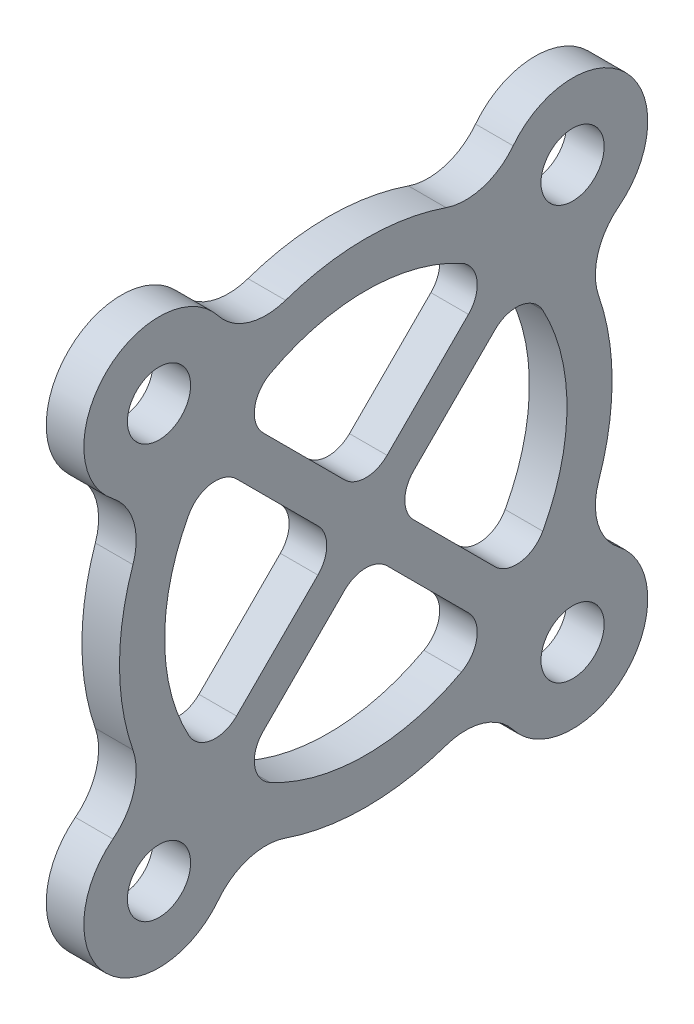
SolidWorks part; units mm, degrees
material "AR500"
ref_plane "Front Plane" through (0, 0, 0) normal (0, 0, 1) x (1, 0, 0)
ref_plane "Top Plane" through (0, 0, 0) normal (0, 1, 0) x (1, 0, 0)
ref_plane "Right Plane" through (0, 0, 0) normal (1, 0, 0) x (0, 0, -1)
ref_plane "Plane1" through (-36.325, 0, 0) normal (-1, 0, 0) x (0, 0, 1)
sketch "Sketch1" plane through (-36.325, 0, 0) normal (-1, 0, 0) x (0, 0, 1)
  arc A0 (-11.1136, 17.582) -> (-17.582, 11.1136) centre (-17.4625, 17.4625) ccw
  arc A1 (-17.582, -11.1136) -> (-11.1136, -17.582) centre (-17.4625, -17.4625) ccw
  arc A2 (11.1136, -17.582) -> (17.582, -11.1136) centre (17.4625, -17.4625) ccw
  arc A3 (17.582, 11.1136) -> (11.1136, 17.582) centre (17.4625, 17.4625) ccw
  arc A4 (20.5884, 11.9352) -> (23.4945, 19.4469) centre (17.4625, 17.4625) ccw construction
  arc A5 (-23.4945, 19.4469) -> (-20.5884, 11.9352) centre (-17.4625, 17.4625) ccw construction
  arc A6 (-20.5884, -11.9352) -> (-23.4945, -19.4469) centre (-17.4625, -17.4625) ccw construction
  arc A7 (23.4945, -19.4469) -> (20.5884, -11.9352) centre (17.4625, -17.4625) ccw construction
  circle A9 centre (-17.4625, -17.4625) radius 2.667 construction
  circle A10 centre (17.4625, 17.4625) radius 2.667 construction
  circle A11 centre (-17.4625, 17.4625) radius 2.667 construction
  circle A12 centre (17.4625, -17.4625) radius 2.667
  circle A13 centre (-17.4625, -17.4625) radius 2.667
  circle A14 centre (17.4625, 17.4625) radius 2.667
  circle A15 centre (-17.4625, 17.4625) radius 2.667
  arc A16 (-17.582, 11.1136) -> (-17.582, -11.1136) centre (0, 0) ccw
  arc A17 (11.1136, 17.582) -> (-11.1136, 17.582) centre (0, 0) ccw
  arc A18 (17.582, -11.1136) -> (17.582, 11.1136) centre (0, 0) ccw
  arc A19 (-11.1136, -17.582) -> (11.1136, -17.582) centre (0, 0) ccw
  dimension "D1" = 41.6
extrude "Boss-Extrude1" add sketch "Sketch1" along normal blind 3.175
fillet "Fillet1" radius 5.08 8 edges at (-37.9125, 17.582, 11.1136) (-37.9125, 11.1136, 17.582) (-37.9125, -11.1136, 17.582) (-37.9125, -17.582, 11.1136) (-37.9125, -17.582, -11.1136) (-37.9125, -11.1136, -17.582) (-37.9125, 17.582, -11.1136) (-37.9125, 11.1136, -17.582)
sketch "Sketch3" plane through (-39.5, 0, 0) normal (-1, 0, 0) x (0, 0, 1)
  circle A9 centre (0, 0) radius 16.99
  arc A10 (19.6653, -6.7762) -> (19.6653, 6.7762) centre (0, 0) ccw construction
  dimension "D1" = 3.81
extrude "Cut-Extrude1" cut sketch "Sketch3" against normal through all
sketch "Sketch4" plane through (-39.5, 0, 0) normal (-1, 0, 0) x (0, 0, 1)
  line L0 (-15.5766, 15.5766) -> (15.5766, -15.5766)
  line L1 (-15.5766, -15.5766) -> (15.5766, 15.5766)
  circle A0 centre (-17.4625, 17.4625) radius 2.667 construction
  circle A1 centre (17.4625, -17.4625) radius 2.667 construction
  circle A2 centre (-17.4625, -17.4625) radius 2.667 construction
  circle A3 centre (17.4625, 17.4625) radius 2.667 construction
  point P13 (17.4625, 17.4625)
extrude "Extrude-Thin1" add sketch "Sketch4" against normal up to surface (3.175 mm away) thin up to face at (-36.325, 0, 16.99) thin type mid plane wall 3.175
fillet "Fillet2" radius 2.54 12 edges at (-37.9125, -13.0837, 10.8387) (-37.9125, -2.2451, 0) (-37.9125, -13.0837, -10.8387) (-37.9125, 0, 2.2451) (-37.9125, -10.8387, 13.0837) (-37.9125, -10.8387, -13.0837) (-37.9125, 0, -2.2451) (-37.9125, 10.8387, -13.0837) (-37.9125, 10.8387, 13.0837) (-37.9125, 2.2451, 0) (-37.9125, 13.0837, -10.8387) (-37.9125, 13.0837, 10.8387)
equation "\"D1@Sketch1\"=41.6mm"
